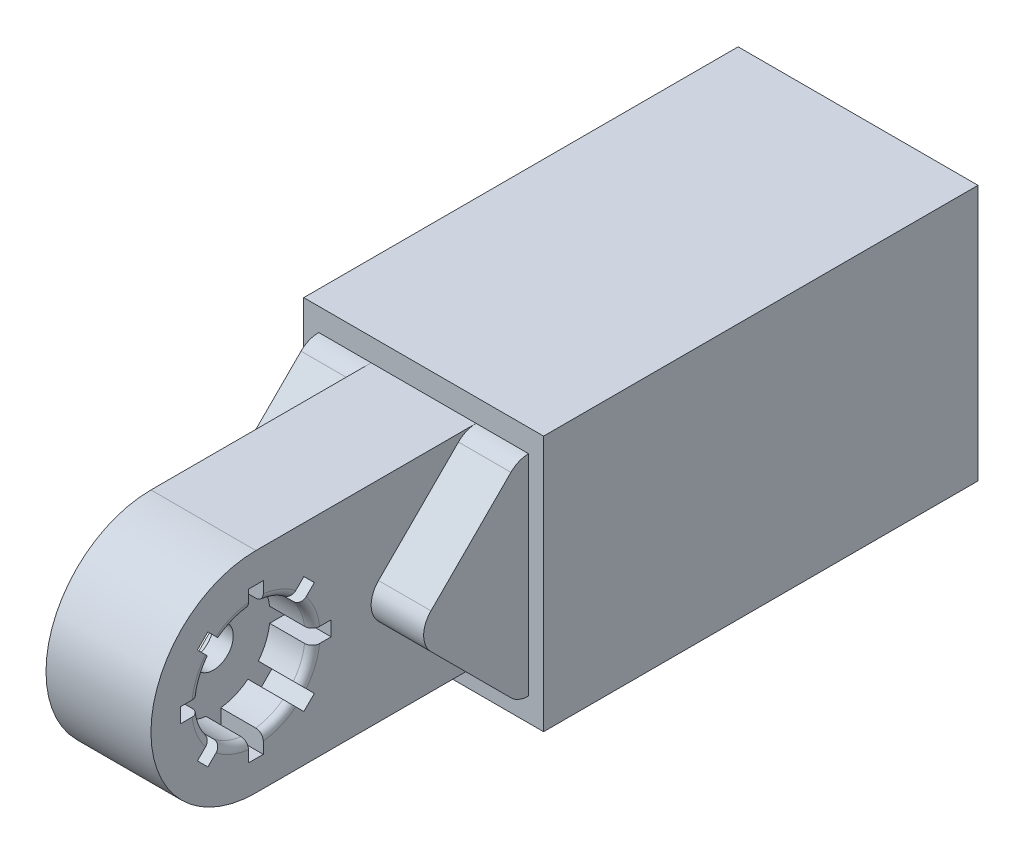
SolidWorks part; units mm, degrees
ref_plane "Front Plane" through (0, 0, 0) normal (0, 0, 1) x (1, 0, 0)
ref_plane "Top Plane" through (0, 0, 0) normal (0, 1, 0) x (1, 0, 0)
ref_plane "Right Plane" through (0, 0, 0) normal (1, 0, 0) x (0, 0, -1)
sketch "Sketch2" plane through (0, 0, 0) normal (0, 0, 1) x (1, 0, 0)
  line L1 (-21, 21) -> (21, 21)
  line L2 (-21, 21) -> (-21, -21)
  line L3 (-21, -21) -> (21, -21)
  line L4 (21, 21) -> (21, -21)
  line L5 (-21, 21) -> (21, -21) construction
  line L6 (-21, -21) -> (21, 21) construction
  point P0 (0, 0)
  dimension "D1" = 42
  dimension "D2" = 42
extrude "Boss-Extrude1" add sketch "Sketch2" along normal blind 89
ref_plane "Plane1" through (0, 0, 89) normal (0, 0, 1) x (1, 0, 0)
sketch "Sketch3" plane through (0, 0, 89) normal (0, 0, 1) x (1, 0, 0)
  line L0 (21, 21) -> (-21, 21) construction
  line L1 (10.5, -21) -> (-10.5, -21)
  line L2 (10.5, -21) -> (10.5, 21)
  line L3 (10.5, 21) -> (-10.5, 21)
  line L4 (-10.5, -21) -> (-10.5, 21)
  line L5 (10.5, -21) -> (-10.5, 21) construction
  line L6 (10.5, 21) -> (-10.5, -21) construction
  point P0 (0, 0)
  dimension "D1" = 21
ref_plane "Plane4" through (0, 0, 0) normal (0, 0, -1) x (-1, 0, 0)
extrude "Boss-Extrude2" add sketch "Sketch3" along normal blind 42
ref_plane "Plane5" through (-10.5, 0, 0) normal (-1, 0, 0) x (0, 0, 1)
sketch "Sketch8" plane through (-10.5, 0, 0) normal (-1, 0, 0) x (0, 0, 1)
  line L0 (131, 21) -> (131, -21) construction
  line L1 (131, 21) -> (131, -21)
  arc A0 (131, 21) -> (131, -21) centre (131, 0) cw
  dimension "D1" = 21
extrude "Boss-Extrude3" add sketch "Sketch8" against normal blind 21
ref_plane "Plane6" through (-10.5, 0, 0) normal (-1, 0, 0) x (0, 0, 1)
sketch "Sketch9" plane through (-10.5, 0, 0) normal (-1, 0, 0) x (0, 0, 1)
  line L0 (89, 21) -> (89, -21) construction
  line L1 (131, 21) -> (131, -21)
  circle A0 centre (131, 0) radius 11.35
  dimension "D1" = 42
  dimension "D2" = 22.7
extrude "Cut-Extrude2" cut sketch "Sketch9" against normal blind 8.5 contours A0
ref_plane "Plane7" through (10.5, 0, 0) normal (1, 0, 0) x (0, 0, -1)
sketch "Sketch11" plane through (10.5, 0, 0) normal (1, 0, 0) x (0, 0, -1)
  line L0 (-131, 21) -> (-131, -21)
  circle A0 centre (-131, 0) radius 11.35
  dimension "D1" = 22.7
extrude "Cut-Extrude3" cut sketch "Sketch11" against normal blind 8.5 contours A0
ref_plane "Plane8" through (-2, 0, 0) normal (-1, 0, 0) x (0, 0, 1)
sketch "Sketch12" plane through (-2, 0, 0) normal (-1, 0, 0) x (0, 0, 1)
  circle A0 centre (131, 0) radius 3.975
  dimension "D1" = 7.95
extrude "Cut-Extrude4" cut sketch "Sketch12" against normal through all
ref_plane "Plane10" through (-2, 0, 0) normal (-1, 0, 0) x (0, 0, 1)
ref_plane "Plane11" through (-10.5, 0, 0) normal (-1, 0, 0) x (0, 0, 1)
sketch "Sketch20" plane through (-10.5, 0, 0) normal (-1, 0, 0) x (0, 0, 1)
  line L0 (131, 0) -> (110, 0)
  line L1 (110, 0) -> (110, 21)
  line L2 (110, 0) -> (110, -21)
  line L4 (110, 21) -> (89, 21)
  line L6 (110, -21) -> (89, -21)
  line L7 (89, 21) -> (110, 0)
  line L8 (89, -21) -> (110, 0)
  line L9 (89, 21) -> (89, -21)
  circle A0 centre (131, 0) radius 11.35
  dimension "D1" = 21
extrude "Boss-Extrude4" add sketch "Sketch20" along normal blind 10.5 and the other way blind 31.5 contours L7 L9 L8 region at (-10.5, 0, 96)
fillet "Fillet1" radius 5 1 edges at (15.75, 0, 110)
fillet "Fillet2" radius 5 1 edges at (-15.75, 0, 110)
fillet "Fillet3" radius 5 1 edges at (-15.75, -21, 89)
fillet "Fillet4" radius 5 1 edges at (-15.75, 21, 89)
fillet "Fillet5" radius 5 1 edges at (15.75, -21, 89)
fillet "Fillet6" radius 5 1 edges at (15.75, 21, 89)
fillet "Fillet7" radius 1.5 1 edges at (-10.5, 0, 142.35)
fillet "Fillet8" radius 1.5 1 edges at (10.5, 0, 119.65)
sketch "Sketch21" plane through (-10.5, 0, 0) normal (-1, 0, 0) x (0, 0, 1)
  line L1 (129.5207, 10.6415) -> (132.4793, 10.6415)
  line L2 (129.5207, 10.6415) -> (129.5207, 15.0585)
  line L3 (129.5207, 15.0585) -> (132.4793, 15.0585)
  line L4 (132.4793, 10.6415) -> (132.4793, 15.0585)
  line L5 (129.5207, 10.6415) -> (132.4793, 15.0585) construction
  line L6 (129.5207, 15.0585) -> (132.4793, 10.6415) construction
  circle A0 centre (131, 0) radius 12.85 construction
  point P0 (131, 12.85)
  dimension "D1" = 4.417
extrude "Cut-Extrude5" cut sketch "Sketch21" against normal blind 8.5
pattern_circular "CirPattern2" count 8 over 360 about axis through (-9, 0, 131) along (-1, 0, 0) of "Cut-Extrude5"
ref_plane "Plane12" through (0, 21, 0) normal (0, 1, 0) x (1, 0, 0)
ref_plane "Plane13" through (10.5, 0, 0) normal (1, 0, 0) x (0, 0, -1)
ref_plane "Plane14" through (0, 0, 0) normal (1, 0, 0) x (0, 0, -1)
mirror "Mirror1" about plane through (0, 0, 0) normal (1, 0, 0) of "CirPattern2"
ref_plane "Plane15" through (21, 0, 0) normal (1, 0, 0) x (0, 0, -1)
sketch "Sketch24" plane through (21, 0, 0) normal (1, 0, 0) x (0, 0, -1)
  line L1 (-86.9289, 21) -> (0, 21)
  line L2 (-86.9289, 21) -> (-86.9289, 25.5452)
  line L3 (-86.9289, 25.5452) -> (0, 25.5452)
  line L4 (0, 21) -> (0, 25.5452)
  line L5 (-86.9289, -21) -> (0, -21)
  line L6 (-86.9289, -21) -> (-86.9289, -25.6891)
  line L7 (-86.9289, -25.6891) -> (0, -25.6891)
  line L8 (0, -21) -> (0, -25.6891)
extrude "Boss-Extrude6" add sketch "Sketch24" against normal blind 42
sketch "Sketch25" plane through (21, 0, 0) normal (1, 0, 0) x (0, 0, -1)
  line L1 (-86.9289, 25.5452) -> (0, 25.5452)
  line L2 (-86.9289, 25.5452) -> (-86.9289, -25.6891)
  line L3 (-86.9289, -25.6891) -> (0, -25.6891)
  line L4 (0, 25.5452) -> (0, -25.6891)
extrude "Boss-Extrude7" add sketch "Sketch25" along normal blind 3
ref_plane "Plane18" through (0, 0, 0) normal (0, 0, -1) x (-1, 0, 0)
ref_plane "Plane19" through (-21, 0, 0) normal (-1, 0, 0) x (0, 0, 1)
sketch "Sketch28" plane through (-21, 0, 0) normal (-1, 0, 0) x (0, 0, 1)
  line L0 (86.9289, -25.6891) -> (0, -25.6891) construction
  line L1 (86.9289, 25.5452) -> (0, 25.5452)
  line L2 (86.9289, 25.5452) -> (86.9289, -25.6891)
  line L3 (86.9289, -25.6891) -> (0, -25.6891)
  line L4 (0, 25.5452) -> (0, -25.6891)
extrude "Boss-Extrude8" add sketch "Sketch28" along normal blind 3
ref_plane "Plane20" through (-24, 0, 0) normal (-1, 0, 0) x (0, 0, 1)
sketch "Sketch30" plane through (-24, 0, 0) normal (-1, 0, 0) x (0, 0, 1)
  line L1 (81.9289, 20.4302) -> (19.9289, 20.4302)
  line L2 (81.9289, 20.4302) -> (81.9289, -20.5741)
  line L3 (81.9289, -20.5741) -> (19.9289, -20.5741)
  line L4 (19.9289, 20.4302) -> (19.9289, -20.5741)
  line L5 (81.9289, 20.4302) -> (19.9289, -20.5741) construction
  line L6 (81.9289, -20.5741) -> (19.9289, 20.4302) construction
  line L8 (86.9289, 25.5452) -> (0, 25.5452) construction
  line L9 (0, -25.6891) -> (86.9289, -25.6891) construction
  line L10 (86.9289, -21) -> (86.9289, 21) construction
  point P0 (50.9289, -0.0719)
  dimension "D1" = 5.115
  dimension "D2" = 5.115
  dimension "D3" = 62
  dimension "D4" = 5
extrude "Cut-Extrude6" cut sketch "Sketch30" against normal blind 45
